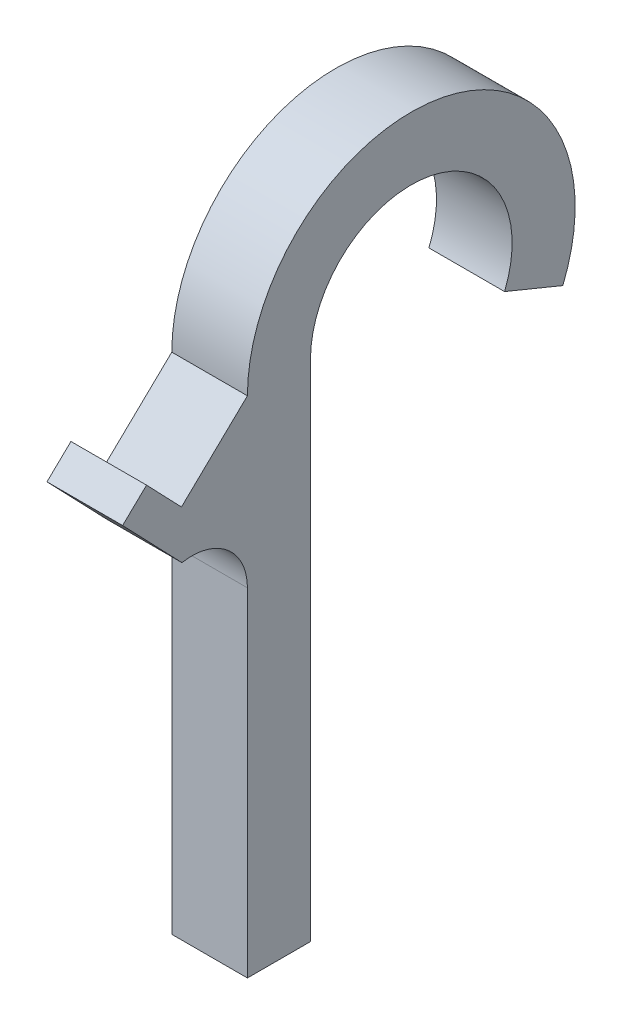
SolidWorks part; units mm, degrees
material "PLA"
ref_plane "Front Plane" through (0, 0, 0) normal (0, 0, 1) x (1, 0, 0)
ref_plane "Top Plane" through (0, 0, 0) normal (0, 1, 0) x (1, 0, 0)
ref_plane "Right Plane" through (0, 0, 0) normal (1, 0, 0) x (0, 0, -1)
sketch "Sketch1" plane through (0, 0, 0) normal (1, 0, 0) x (0, 0, -1)
  line L0 (-5.08, 0) -> (-5.08, -25.4)
  line L1 (4.6991, -1.9301) -> (7.636, -3.1364)
  line L2 (-8.255, -2.464) -> (-8.255, -25.4)
  line L3 (-8.255, -25.4) -> (-5.08, -25.4)
  line L4 (-8.255, 0) -> (-11.5781, -3.1882)
  line L5 (-11.5781, -3.1882) -> (-13.3366, -1.3553)
  line L6 (-13.3366, -1.3553) -> (-14.5436, -2.5133)
  line L7 (-14.5436, -2.5133) -> (-11.5542, -5.6292)
  line L8 (-11.5542, -5.6292) -> (-8.255, -2.464)
  arc A0 (4.6991, -1.9301) -> (-5.08, 0) centre (0, 0) ccw
  arc A1 (7.636, -3.1364) -> (-8.255, 0) centre (0, 0) ccw
  point P13 (-14.6907, -5.0448)
  point P14 (-11.3262, -5.3875)
  dimension "D1" = 10.16
  dimension "D2" = 16.51
  dimension "D3" = 25.4
  dimension "D4" = 67.67
  dimension "D5" = 2.54
  dimension "D6" = 1.6726
  dimension "D7" = 1.778
  dimension "D8" = 4.572
extrude "Boss-Extrude1" add sketch "Sketch1" along normal blind 3.81
fillet "Fillet1" radius 2.794 1 edges at (1.905, -2.464, 8.255)
